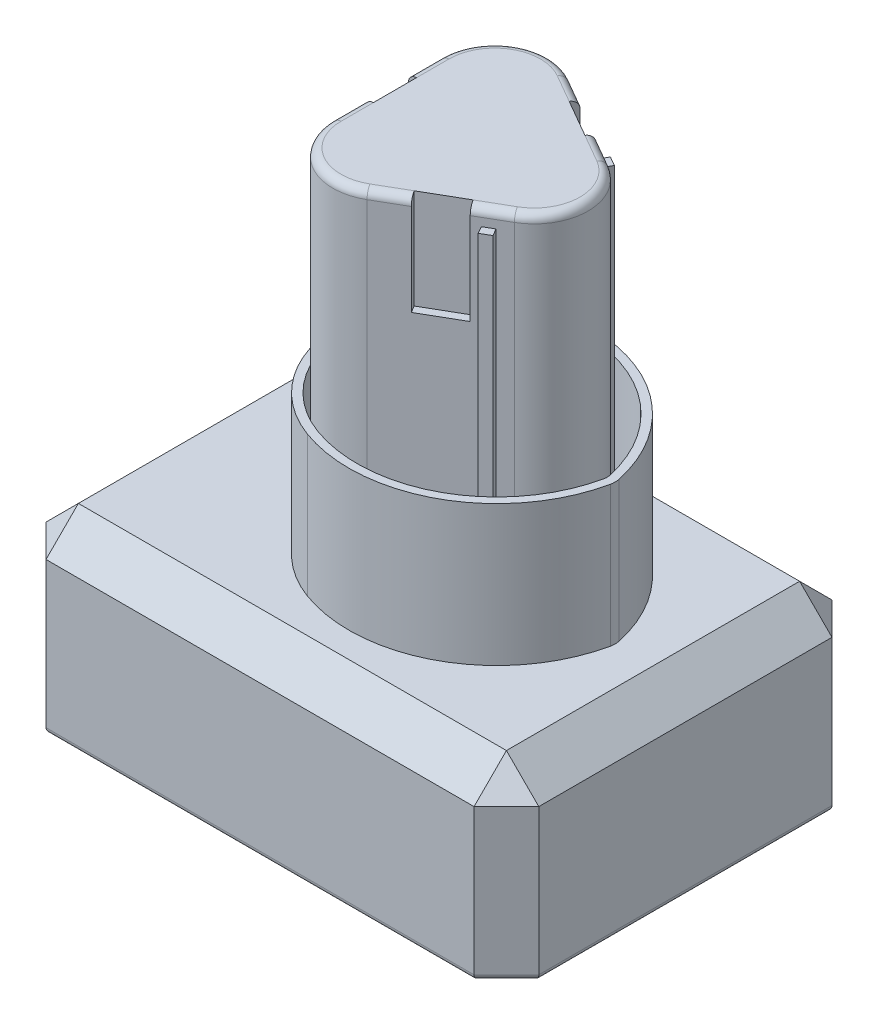
SolidWorks part; units mm, degrees
ref_plane "Front Plane" through (0, 0, 0) normal (0, 0, 1) x (1, 0, 0)
ref_plane "Top Plane" through (0, 0, 0) normal (0, 1, 0) x (1, 0, 0)
ref_plane "Right Plane" through (0, 0, 0) normal (1, 0, 0) x (0, 0, -1)
sketch "Sketch1" plane through (0, 0, 0) normal (0, 1, 0) x (1, 0, 0)
  line L0 (46, 43.175) -> (46, 23.175) construction
  line L1 (0, 0) -> (91.35, 0)
  line L2 (0, 0) -> (0, 66.35)
  line L3 (0, 66.35) -> (91.35, 66.35)
  line L4 (91.35, 0) -> (91.35, 66.35)
  line L5 (46, 23.175) -> (63.3205, 33.175) construction
  line L6 (63.3205, 33.175) -> (46, 43.175) construction
  line L7 (36, 43.175) -> (36, 23.175)
  line L8 (51, 14.5147) -> (68.3205, 24.5147)
  line L9 (51, 51.8353) -> (68.3205, 41.8353)
  line L10 (73.3205, 37.0199) -> (73.3205, 30.0976) construction
  line L11 (56.1962, 48.8353) -> (55.4462, 47.5362)
  line L12 (55.4462, 47.5362) -> (62.3744, 43.5362)
  line L13 (62.3744, 43.5362) -> (63.1244, 44.8353)
  line L14 (63.1244, 44.8353) -> (56.1962, 48.8353)
  line L15 (63.1244, 21.5147) -> (62.3744, 22.8138)
  line L16 (62.3744, 22.8138) -> (55.4462, 18.8138)
  line L17 (55.4462, 18.8138) -> (56.1962, 17.5147)
  line L18 (56.1962, 17.5147) -> (63.1244, 21.5147)
  line L19 (36, 37.175) -> (37.5, 37.175)
  line L20 (37.5, 37.175) -> (37.5, 29.175)
  line L21 (37.5, 29.175) -> (36, 29.175)
  line L22 (36, 29.175) -> (36, 37.175)
  line L23 (58.9103, 45.5362) -> (59.6603, 46.8353) construction
  line L24 (58.9103, 20.8138) -> (59.6603, 19.5147) construction
  line L25 (64.4234, 44.0853) -> (65.1984, 45.4276)
  line L26 (65.1984, 45.4276) -> (66.9304, 44.4276)
  line L27 (66.9304, 44.4276) -> (66.1554, 43.0853)
  line L28 (66.1554, 43.0853) -> (64.4234, 44.0853)
  line L29 (66.1554, 23.2647) -> (66.9304, 21.9224)
  line L30 (66.9304, 21.9224) -> (65.1984, 20.9224)
  line L31 (65.1984, 20.9224) -> (64.4234, 22.2647)
  line L32 (64.4234, 22.2647) -> (66.1554, 23.2647)
  arc A0 (68.3205, 24.5147) -> (68.3205, 41.8353) centre (63.3205, 33.175) ccw
  arc A1 (51, 51.8353) -> (36, 43.175) centre (46, 43.175) ccw
  arc A2 (36, 23.175) -> (51, 14.5147) centre (46, 23.175) ccw
  arc A3 (42.5772, 52.571) -> (42.5772, 13.779) centre (49.6429, 33.175) ccw
  arc A4 (42.5772, 52.571) -> (76.7688, 33.6626) centre (51.4427, 28.2341) cw
  arc A5 (76.7688, 32.6874) -> (42.5772, 13.779) centre (51.4427, 38.1159) cw
  arc A6 (76.7688, 33.6626) -> (76.7688, 32.6874) centre (74.494, 33.175) cw
  arc A7 (42.0638, 53.9804) -> (78.2355, 33.977) centre (51.4427, 28.2341) cw
  arc A8 (78.2355, 33.977) -> (78.2355, 32.373) centre (74.494, 33.175) cw
  arc A9 (78.2355, 32.373) -> (42.0638, 12.3696) centre (51.4427, 38.1159) cw
  arc A10 (42.0638, 53.9804) -> (42.0638, 12.3696) centre (49.6429, 33.175) ccw
  arc A11 (76.7688, 32.6874) -> (42.5772, 13.779) centre (51.4427, 38.1159) cw construction
  point P17 (29, 33.175)
  point P18 (36, 33.175)
  point P19 (91.35, 33.175)
  point P29 (76.8685, 33.175)
  point P30 (76.8205, 33.175)
  point P31 (78.3205, 33.175)
  point P51 (37.5, 33.175)
  point P56 (59.6603, 46.8353)
  point P59 (59.6603, 19.5147)
  dimension "D3" = 20
  dimension "D6" = 8
  dimension "D8" = 36
  dimension "D1" = 91.35
  dimension "D2" = 66.35
  dimension "D4" = 7
  dimension "D5" = 5
  dimension "D9" = 1.5
  dimension "D10" = 2
  dimension "D11" = 1.55
  dimension "D12" = 1.5
  dimension "D13" = 1.5
  dimension "D7" = 1.5
extrude "Boss-Extrude1" add sketch "Sketch1" along normal blind 34 contours L1 L4 L3 L2
chamfer "Chamfer1" distance 6 angle 45 8 edges at (45.675, 34, -66.35) (91.35, 17, -66.35) (91.35, 34, -33.175) (91.35, 17, 0) (45.675, 34, 0) (0, 17, -66.35) (0, 34, -33.175) (0, 17, 0)
sketch "Sketch2" plane through (0, 0, 0) normal (0, -1, 0) x (-1, 0, 0)
  line L0 (-7.175, 8.175) -> (-7.175, 58.175) construction
  line L1 (-4.175, 11.175) -> (-87.175, 11.175) construction
  line L2 (0, 6) -> (0, 60.35) construction
  line L3 (-6, 0) -> (-85.35, 0) construction
  circle A0 centre (-7.175, 11.175) radius 3
  circle A1 centre (-7.175, 55.175) radius 3
  circle A2 centre (-84.175, 55.175) radius 3
  circle A3 centre (-84.175, 11.175) radius 3
  circle A4 centre (-7.175, 11.175) radius 1.5
  circle A5 centre (-7.175, 55.175) radius 1.5
  circle A6 centre (-84.175, 55.175) radius 1.5
  circle A7 centre (-84.175, 11.175) radius 1.5
  point P12 (0, 0)
  point P15 (0, 0)
  point P16 (-83.8382, 53.5351)
  point P21 (0, 33.175)
  point P22 (-7.175, 33.175)
  point P25 (-45.675, 0)
  point P26 (-45.675, 11.175)
  dimension "D2" = 6
  dimension "D3" = 3
  dimension "D1" = 50
  dimension "D4" = 83
extrude "Cut-Extrude1" cut sketch "Sketch2" against normal blind 6 contours A0 A4 | A3 A7 | A1 A5 | A2 A6 region at (10.0901, 0, -11.175) region at (10.0901, 0, -55.175) region at (87.0901, 0, -55.175) region at (87.0901, 0, -11.175)
extrude "Cut-Extrude2" cut sketch "Sketch2<3>" against normal blind 12 contours A4 | A7 | A6 | A5 region at (7.175, 0, -11.175) region at (7.175, 0, -55.175) region at (84.175, 0, -55.175) region at (84.175, 0, -11.175)
sketch "Sketch2<3>" plane through (0, 0, 0) normal (0, -1, 0) x (-1, 0, 0) same geometry as "Sketch2"
fillet "Fillet1" radius 1 8 edges at (3, 0, -63.35) (0, 0, -33.175) (3, 0, -3) (91.35, 0, -33.175) (88.35, 0, -63.35) (45.675, 0, -66.35) (88.35, 0, -3) (45.675, 0, 0)
extrude "Boss-Extrude3" add sketch "Sketch1<5>" along normal blind 68.5 from surface contours L7 A2 L8 L17 L16 L15 A0 L9 L13 L12 L11 A1 L19 L20 L21 | L16 L17 L8 L15 | L21 L20 L19 L7 | L12 L13 L14 L11 region at (51.7735, 0, -33.175) region at (36.75, 0, -33.175) region at (59.2853, 0, -20.1643) starting at face at (45.675, 34, -33.175)
sketch "Sketch1<5>" plane through (0, 0, 0) normal (0, 1, 0) x (1, 0, 0) same geometry as "Sketch1"
extrude "Cut-Extrude3" cut sketch "Sketch1<6>" against normal blind 18.5 from surface contours L12 L13 L9 L11 | L16 L17 L8 L15 | L21 L20 L19 L7 region at (36.75, 0, -33.175) region at (59.2853, 0, -46.1857) region at (59.2853, 0, -20.1643) starting at face at (51.7735, 102.5, -33.175)
sketch "Sketch1<6>" plane through (0, 0, 0) normal (0, 1, 0) x (1, 0, 0) same geometry as "Sketch1"
extrude "Boss-Extrude4" add sketch "Sketch1<7>" along normal blind 65.5 from surface contours L27 L26 L25 L9 | L31 L30 L29 L8 region at (65.6769, 0, -44.2564) region at (65.6769, 0, -22.0936) starting at face at (51.7735, 34, -33.175)
sketch "Sketch1<7>" plane through (0, 0, 0) normal (0, 1, 0) x (1, 0, 0) same geometry as "Sketch1"
fillet "Fillet2" radius 1.5 9 edges at (53.5981, 102.5, -16.0147) (36, 102.5, -26.175) (36, 102.5, -40.175) (53.5981, 102.5, -50.3353) (65.7224, 102.5, -43.3353) (65.7224, 102.5, -23.0147) (41, 102.5, -14.5147) (41, 102.5, -51.8353) (73.3205, 102.5, -33.175)
extrude "Boss-Extrude6" add sketch "Sketch1<8>" along normal blind 26 from surface separate body contours A7 A10 A9 A8 A4 A6 A5 A3 region at (64.3751, 0, -51.6195) starting at face at (59.7183, 34, -33.175)
sketch "Sketch1<8>" plane through (0, 0, 0) normal (0, 1, 0) x (1, 0, 0) same geometry as "Sketch1"
